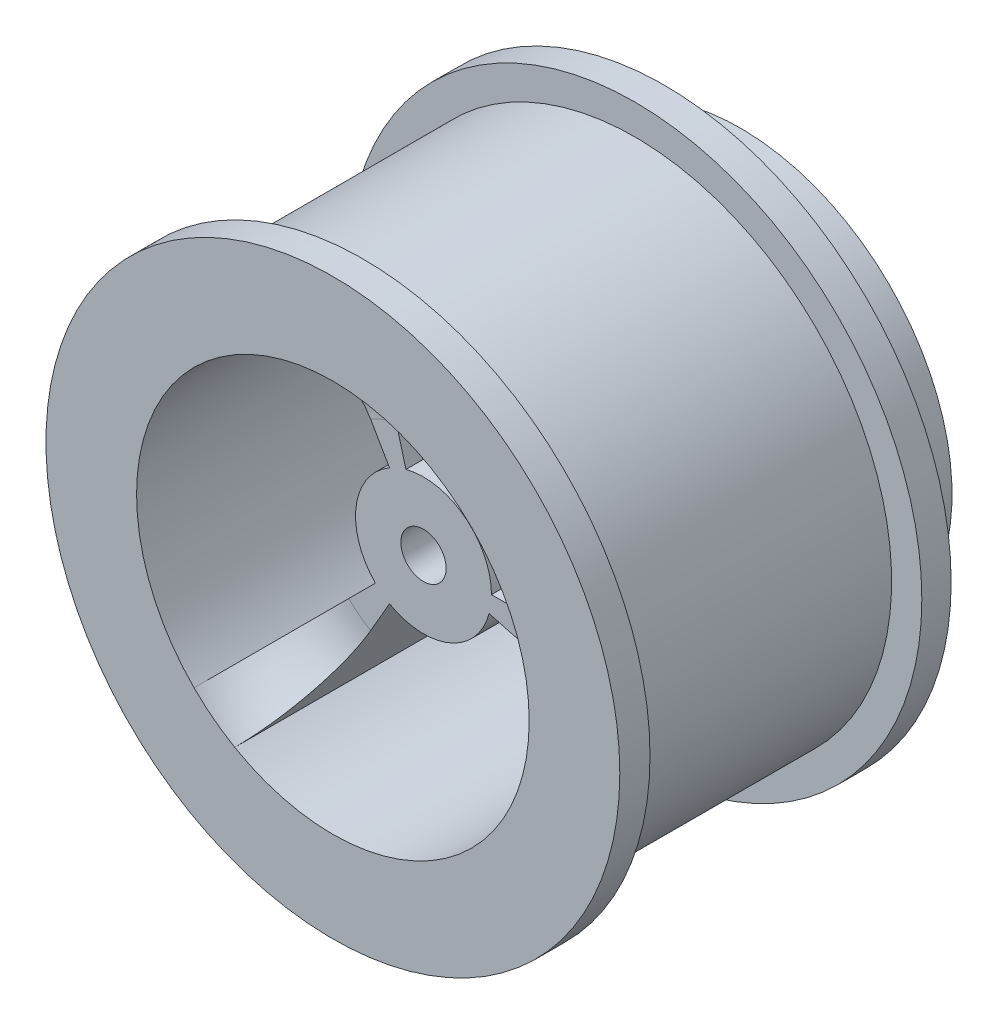
SolidWorks part; units mm, degrees
ref_plane "Front Plane" through (0, 0, 0) normal (0, 0, 1) x (1, 0, 0)
ref_plane "Top Plane" through (0, 0, 0) normal (0, 1, 0) x (1, 0, 0)
ref_plane "Right Plane" through (0, 0, 0) normal (1, 0, 0) x (0, 0, -1)
sketch "Sketch1" plane through (0, 0, 0) normal (0, 0, 1) x (1, 0, 0)
  line L0 (0, 0) -> (0, 8.5) construction
  circle A0 centre (0, 0) radius 6.5
  circle A1 centre (0, 0) radius 8.5
  circle A2 centre (0, 0) radius 0.75
  circle A3 centre (0, 0) radius 2.25
  dimension "D1" = 17
  dimension "D2" = 2
  dimension "D3" = 1.5
  dimension "D4" = 1.5
extrude "Boss-Extrude1" add sketch "Sketch1" along normal blind 9 contours A2 A3 | A0 A1 region at (-8.2596, 0, 0) region at (-2.1864, 0, 0)
sketch "Sketch2" plane through (0, 0, 0) normal (0, 0, -1) x (-1, 0, 0)
  circle A0 centre (0, 0) radius 9.5
  dimension "D1" = 19
extrude "Boss-Extrude2" add sketch "Sketch2" along normal blind 1.5
sketch "Sketch3" plane through (0, 0, 9) normal (0, 0, 1) x (1, 0, 0)
  circle A0 centre (0, 0) radius 6.5
  circle A1 centre (0, 0) radius 9.5
  circle A2 centre (0, 0) radius 6.5 construction
  dimension "D1" = 19
extrude "Boss-Extrude3" add sketch "Sketch3" along normal blind 1
sketch "Sketch5" plane through (0, 0, 9) normal (0, 0, 1) x (1, 0, 0)
  line L0 (0, 0) -> (13.9199, 0) construction
  line L1 (0, 0) -> (12.6765, -3.3967) construction
  line L2 (2.25, 0) -> (6.5, 0)
  line L3 (2.1733, -0.5823) -> (6.2785, -1.6823)
  arc A0 (2.1733, -0.5823) -> (2.25, 0) centre (0, 0) ccw
  circle A1 centre (0, 0) radius 2.25 construction
  arc A2 (6.2785, -1.6823) -> (6.5, 0) centre (0, 0) ccw
  circle A3 centre (0, 0) radius 6.5 construction
  dimension "D1" = 15
extrude "Boss-Extrude4" add sketch "Sketch5" against normal up to next
pattern_circular "CirPattern1" count 3 over 360 about axis through (0, 0, 9) along (0, 0, 1) of "Boss-Extrude4"
sketch "Sketch6" plane through (0, 0, 9) normal (0, 0, 1) x (1, 0, 0)
  circle A0 centre (0, 0) radius 6.5
  arc A2 (-4.5962, -4.5962) -> (-3.25, -5.6292) centre (0, 0) ccw construction
extrude "Cut-Extrude2" cut sketch "Sketch6" against normal blind 2
fillet "Fillet1" radius 3 3 edges at (-2.4874, 6.0052, 7) (-3.9569, -5.1568, 7) (6.4444, -0.8484, 7)
sketch "Sketch8" plane through (0, 0, -1.5) normal (0, 0, -1) x (-1, 0, 0)
  circle A1 centre (0, 0) radius 6.5
  dimension "D1" = 13
extrude "Boss-Extrude5" add sketch "Sketch8" along normal blind 1 contours A1
sketch "Sketch7" plane through (0, 0, 0) normal (0, 0, 1) x (1, 0, 0)
  line L0 (0, 0) -> (12.1676, 0) construction
  line L1 (0, 0) -> (6.4881, -15.6637) construction
  circle A0 centre (1.7221, -4.1575) radius 1
  dimension "D2" = 2
  dimension "D3" = 4.5
  dimension "D1" = 67.5
extrude "Cut-Extrude3" cut sketch "Sketch7" against normal blind 7
pattern_circular "CirPattern2" count 3 over 360 about axis through (0, 0, 7) along (0, 0, 1) of "Cut-Extrude3"
fillet "Fillet2" radius 1 12 edges at (0.861, -2.0787, 0) (1.3697, 1.785, 0) (-2.2308, 0.2937, 0) (3.9569, 5.1568, 0) (2.4874, -6.0052, 0) (-6.4444, 0.8484, 0) (4.375, 0, 0) (4.2259, -1.1323, 0) (-3.0936, -3.0936, 0) (-2.1875, -3.7889, 0) (-1.1323, 4.2259, 0) (-2.1875, 3.7889, 0)
sketch "Sketch10" plane through (0, 0, -2.5) normal (0, 0, -1) x (-1, 0, 0)
  circle A0 centre (0, 0) radius 7
  circle A1 centre (0, 0) radius 6.5 construction
  dimension "D1" = 14
extrude "Boss-Extrude6" add sketch "Sketch10" along normal blind 1
sketch "Sketch11" plane through (0, 0, 0) normal (0, 1, 0) x (1, 0, 0)
  line L0 (-6.5, 2.5) -> (-10.5, 3.2053)
  line L1 (-10.5, 3.2053) -> (-10.5, 0.7947)
  line L2 (-10.5, 0.7947) -> (-6.5, 1.5)
  line L3 (-6.5, 1.5) -> (-6.5, 2.5)
  line L4 (0, 0) -> (0, 9.18) construction
  dimension "D1" = 100
  dimension "D2" = 100
  dimension "D3" = 4
revolve "Cut-Revolve1" cut sketch "Sketch11" angle 360 about L4
sketch "Sketch12" plane through (0, 0, 7) normal (0, 0, 1) x (1, 0, 0)
  circle A0 centre (0, 0) radius 0.75
  dimension "D1" = 1.5
extrude "Cut-Extrude5" cut sketch "Sketch12" against normal blind 14.5
sketch "Sketch13" plane through (0, 0, -3.5) normal (0, 0, -1) x (-1, 0, 0)
  circle A0 centre (0, 0) radius 2.5
  dimension "D1" = 5
extrude "Cut-Extrude6" cut sketch "Sketch13" against normal blind 2.5
